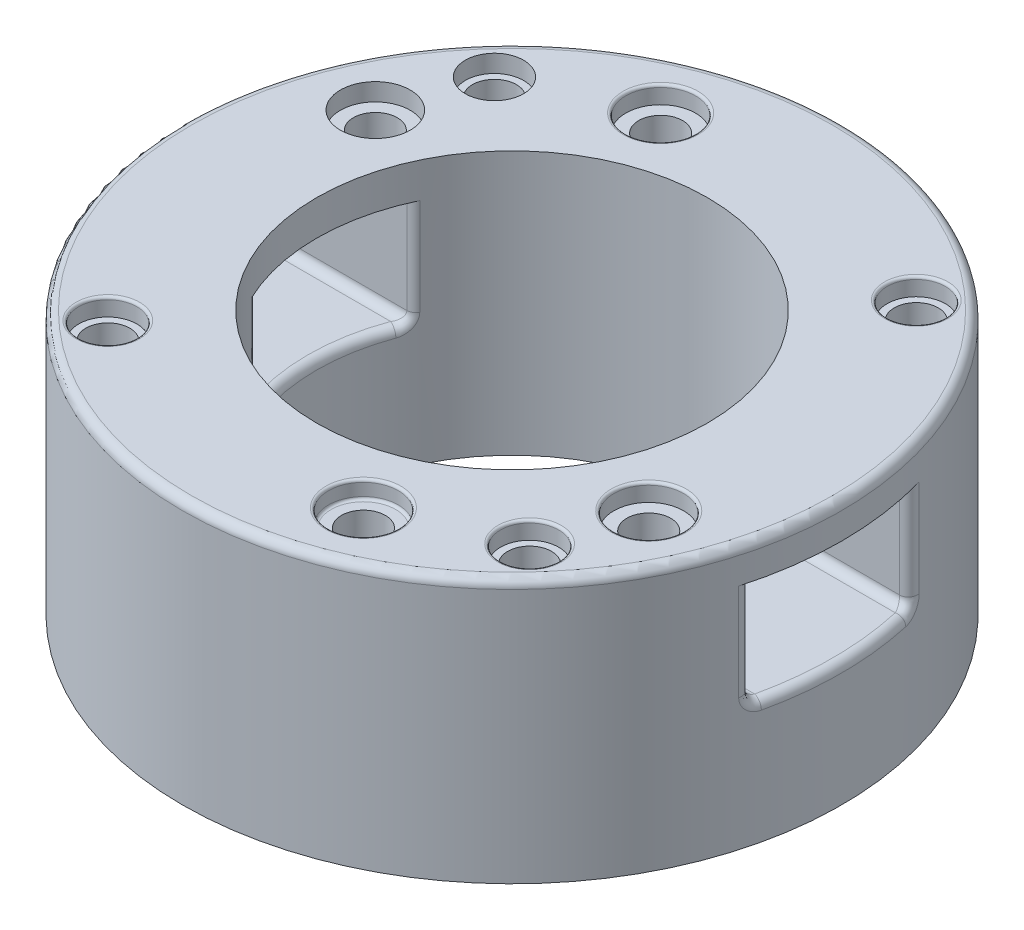
SolidWorks part; units mm, degrees
ref_plane "Front Plane" through (0, 0, 0) normal (0, 0, 1) x (1, 0, 0)
ref_plane "Top Plane" through (0, 0, 0) normal (0, 1, 0) x (1, 0, 0)
ref_plane "Right Plane" through (0, 0, 0) normal (1, 0, 0) x (0, 0, -1)
sketch "Sketch2" plane through (0, 0, 0) normal (0, 1, 0) x (1, 0, 0)
  circle A0 centre (0, 0) radius 37.5
  dimension "D1" = 75
extrude "Boss-Extrude1" add sketch "Sketch2" along normal blind 30
sketch "Sketch4" plane through (0, 30, 0) normal (0, 1, 0) x (1, 0, 0)
  circle A0 centre (0, 0) radius 22.2331
extrude "Cut-Extrude2" cut sketch "Sketch4" against normal blind 70
fillet "Fillet1" radius 1 1 edges at (0, 30, 37.5)
sketch "Sketch5" plane through (0, 30, 0) normal (0, 1, 0) x (1, 0, 0)
  circle A0 centre (22, 24) radius 2.5
  circle A1 centre (24, -22) radius 2.5
  circle A2 centre (-22, -24) radius 2.5
  circle A3 centre (-24, 22) radius 2.5
  point P12 (0, 0)
  dimension "D1" = 5
  dimension "D2" = 24
  dimension "D3" = 22
  dimension "D4" = 4
extrude "Cut-Extrude3" cut sketch "Sketch5" against normal blind 65
sketch "Sketch6" plane through (0, 0, 0) normal (0, -1, 0) x (1, 0, 0)
  line L1 (-7, -39.9079) -> (7, -39.9079)
  line L2 (-7, -39.9079) -> (-7, 39.9079)
  line L3 (-7, 39.9079) -> (7, 39.9079)
  line L4 (7, -39.9079) -> (7, 39.9079)
  line L5 (-7, -39.9079) -> (7, 39.9079) construction
  line L6 (-7, 39.9079) -> (7, -39.9079) construction
  point P0 (0, 0)
  dimension "D1" = 14
sketch "Sketch7" plane through (0, 0, 0) normal (1, 0, 0) x (0, 0, -1)
  line L1 (-9, 26) -> (9, 26)
  line L2 (-9, 26) -> (-9, 14)
  line L3 (-9, 14) -> (9, 14)
  line L4 (9, 26) -> (9, 14)
  line L5 (-9, 26) -> (9, 14) construction
  line L6 (-9, 14) -> (9, 26) construction
  point P0 (0, 20)
  dimension "D1" = 12
  dimension "D2" = 18
  dimension "D3" = 20
  dimension "D4" = 9
  dimension "D5" = 0
extrude "Cut-Extrude6" cut sketch "Sketch7" against normal mid plane 120
fillet "Fillet3" radius 1 8 edges at (36.404, 20, -9) (36.404, 20, 9) (20.33, 20, 9) (20.33, 20, -9) (37.5, 14, 0) (28.367, 14, 9) (22.2331, 14, 0) (28.367, 14, -9)
fillet "Fillet4" radius 1 8 edges at (-36.404, 20, 9) (-36.404, 20, -9) (-20.33, 20, -9) (-20.33, 20, 9) (-37.5, 14, 0) (-28.367, 14, -9) (-22.2331, 14, 0) (-28.367, 14, 9)
sketch "Sketch8" plane through (0, 30, 0) normal (0, 1, 0) x (1, 0, 0)
  circle A0 centre (11, -27.9106) radius 2.5
  circle A1 centre (24, -22) radius 2.5 construction
  circle A2 centre (27.5139, -11.9576) radius 2.5
  circle A3 centre (0, 0) radius 22.2331 construction
  circle A4 centre (-11, 27.9106) radius 2.5
  circle A5 centre (-27.5139, 11.9576) radius 2.5
  point P9 (0, 0)
  point P17 (0, 0)
  dimension "D2" = 5
  dimension "D1" = 30
  dimension "D3" = 13
  dimension "D5" = 2
  dimension "D4" = 2
extrude "Cut-Extrude7" cut sketch "Sketch8" against normal blind 50
sketch "Sketch9" plane through (0, 30, 0) normal (0, 1, 0) x (1, 0, 0)
  circle A0 centre (-27.5139, 11.9576) radius 3.9696
  circle A1 centre (-11, 27.9106) radius 3.9696
  circle A2 centre (27.5139, -11.9576) radius 3.9696
  circle A3 centre (11, -27.9106) radius 3.9696
  point P5 (-11, 27.9106)
  point P9 (27.5139, -11.9576)
  point P13 (11, -27.9106)
extrude "Cut-Extrude8" cut sketch "Sketch9" against normal blind 2
sketch "Sketch10" plane through (0, 30, 0) normal (0, 1, 0) x (1, 0, 0)
  circle A0 centre (-22, -24) radius 3.314
  circle A1 centre (-24, 22) radius 3.314
  circle A2 centre (22, 24) radius 3.314
  circle A3 centre (24, -22) radius 3.314
  point P3 (0, 0)
  point P6 (-24, 22)
  point P8 (22, 24)
  point P14 (24, -22)
extrude "Cut-Extrude9" cut sketch "Sketch10" against normal blind 2
fillet "Fillet5" radius 0.3 7 edges at (11, 30, 31.8801) (11, 28, 31.8801) (-22, 30, 27.314) (24, 30, 25.314) (22, 30, -20.686) (27.5139, 30, 15.9271) (-11, 30, -23.941)
